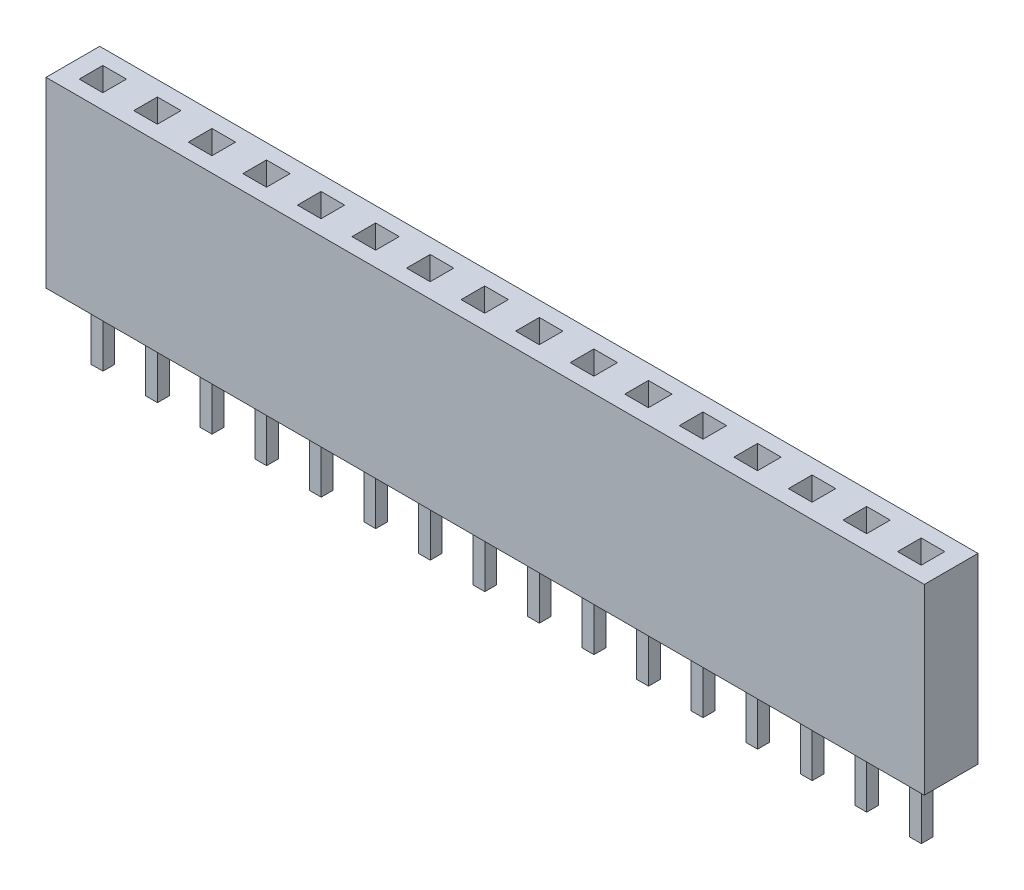
SolidWorks part; units mm, degrees
ref_plane "Front Plane" through (0, 0, 0) normal (0, 0, 1) x (1, 0, 0)
ref_plane "Top Plane" through (0, 0, 0) normal (0, 1, 0) x (1, 0, 0)
ref_plane "Right Plane" through (0, 0, 0) normal (1, 0, 0) x (0, 0, -1)
sketch "Sketch1" plane through (0, 0, 0) normal (0, 0, 1) x (1, 0, 0)
  line L1 (0, 0) -> (40.89, 0)
  line L2 (0, 0) -> (0, 8.5)
  line L3 (0, 8.5) -> (40.89, 8.5)
  line L4 (40.89, 0) -> (40.89, 8.5)
  dimension "D1" = 8.5
  dimension "D2" = 40.89
extrude "Boss-Extrude1" add sketch "Sketch1" along normal mid plane 2.5
sketch "Sketch2" plane through (0, 0, 0) normal (0, -1, 0) x (1, 0, 0)
  line L0 (0, 0) -> (40.89, 0) construction
  line L1 (40.89, 1.25) -> (40.89, -1.25) construction
  line L2 (3.385, -0.55) -> (4.485, -0.55)
  line L3 (0.845, -0.55) -> (1.945, -0.55)
  line L4 (0.845, -0.55) -> (0.845, 0.55)
  line L5 (0.845, 0.55) -> (1.945, 0.55)
  line L6 (1.945, -0.55) -> (1.945, 0.55)
  line L7 (0.845, -0.55) -> (1.945, 0.55) construction
  line L8 (0.845, 0.55) -> (1.945, -0.55) construction
  line L9 (3.385, -0.55) -> (3.385, 0.55)
  line L10 (3.385, 0.55) -> (4.485, 0.55)
  line L11 (4.485, -0.55) -> (4.485, 0.55)
  line L12 (3.385, -0.55) -> (4.485, 0.55) construction
  line L13 (3.385, 0.55) -> (4.485, -0.55) construction
  line L14 (5.925, -0.55) -> (7.025, -0.55)
  line L15 (5.925, -0.55) -> (5.925, 0.55)
  line L16 (5.925, 0.55) -> (7.025, 0.55)
  line L17 (7.025, -0.55) -> (7.025, 0.55)
  line L18 (5.925, -0.55) -> (7.025, 0.55) construction
  line L19 (5.925, 0.55) -> (7.025, -0.55) construction
  line L20 (8.465, -0.55) -> (9.565, -0.55)
  line L21 (8.465, -0.55) -> (8.465, 0.55)
  line L22 (8.465, 0.55) -> (9.565, 0.55)
  line L23 (9.565, -0.55) -> (9.565, 0.55)
  line L24 (8.465, -0.55) -> (9.565, 0.55) construction
  line L25 (8.465, 0.55) -> (9.565, -0.55) construction
  line L26 (11.005, -0.55) -> (12.105, -0.55)
  line L27 (11.005, -0.55) -> (11.005, 0.55)
  line L28 (11.005, 0.55) -> (12.105, 0.55)
  line L29 (12.105, -0.55) -> (12.105, 0.55)
  line L30 (11.005, -0.55) -> (12.105, 0.55) construction
  line L31 (11.005, 0.55) -> (12.105, -0.55) construction
  line L32 (13.545, -0.55) -> (14.645, -0.55)
  line L33 (13.545, -0.55) -> (13.545, 0.55)
  line L34 (13.545, 0.55) -> (14.645, 0.55)
  line L35 (14.645, -0.55) -> (14.645, 0.55)
  line L36 (13.545, -0.55) -> (14.645, 0.55) construction
  line L37 (13.545, 0.55) -> (14.645, -0.55) construction
  line L38 (16.085, -0.55) -> (17.185, -0.55)
  line L39 (16.085, -0.55) -> (16.085, 0.55)
  line L40 (16.085, 0.55) -> (17.185, 0.55)
  line L41 (17.185, -0.55) -> (17.185, 0.55)
  line L42 (16.085, -0.55) -> (17.185, 0.55) construction
  line L43 (16.085, 0.55) -> (17.185, -0.55) construction
  line L44 (18.625, -0.55) -> (19.725, -0.55)
  line L45 (18.625, -0.55) -> (18.625, 0.55)
  line L46 (18.625, 0.55) -> (19.725, 0.55)
  line L47 (19.725, -0.55) -> (19.725, 0.55)
  line L48 (18.625, -0.55) -> (19.725, 0.55) construction
  line L49 (18.625, 0.55) -> (19.725, -0.55) construction
  line L54 (21.165, -0.55) -> (22.265, -0.55)
  line L55 (21.165, -0.55) -> (21.165, 0.55)
  line L60 (21.165, 0.55) -> (22.265, 0.55)
  line L61 (22.265, -0.55) -> (22.265, 0.55)
  line L66 (21.165, -0.55) -> (22.265, 0.55) construction
  line L67 (21.165, 0.55) -> (22.265, -0.55) construction
  line L72 (23.705, -0.55) -> (24.805, -0.55)
  line L73 (23.705, -0.55) -> (23.705, 0.55)
  line L78 (1.395, 0) -> (3.935, 0) construction
  line L79 (23.705, 0.55) -> (24.805, 0.55)
  line L80 (24.805, -0.55) -> (24.805, 0.55)
  line L81 (23.705, -0.55) -> (24.805, 0.55) construction
  line L82 (23.705, 0.55) -> (24.805, -0.55) construction
  line L83 (26.245, -0.55) -> (27.345, -0.55)
  line L84 (26.245, -0.55) -> (26.245, 0.55)
  line L85 (26.245, 0.55) -> (27.345, 0.55)
  line L86 (27.345, -0.55) -> (27.345, 0.55)
  line L87 (26.245, -0.55) -> (27.345, 0.55) construction
  line L88 (26.245, 0.55) -> (27.345, -0.55) construction
  line L89 (28.785, -0.55) -> (29.885, -0.55)
  line L90 (28.785, -0.55) -> (28.785, 0.55)
  line L91 (28.785, 0.55) -> (29.885, 0.55)
  line L92 (29.885, -0.55) -> (29.885, 0.55)
  line L93 (28.785, -0.55) -> (29.885, 0.55) construction
  line L94 (28.785, 0.55) -> (29.885, -0.55) construction
  line L95 (31.325, -0.55) -> (32.425, -0.55)
  line L96 (31.325, -0.55) -> (31.325, 0.55)
  line L97 (31.325, 0.55) -> (32.425, 0.55)
  line L98 (32.425, -0.55) -> (32.425, 0.55)
  line L99 (31.325, -0.55) -> (32.425, 0.55) construction
  line L100 (31.325, 0.55) -> (32.425, -0.55) construction
  line L101 (33.865, -0.55) -> (34.965, -0.55)
  line L102 (33.865, -0.55) -> (33.865, 0.55)
  line L103 (33.865, 0.55) -> (34.965, 0.55)
  line L104 (34.965, -0.55) -> (34.965, 0.55)
  line L105 (33.865, -0.55) -> (34.965, 0.55) construction
  line L106 (33.865, 0.55) -> (34.965, -0.55) construction
  line L107 (36.405, -0.55) -> (37.505, -0.55)
  line L108 (36.405, -0.55) -> (36.405, 0.55)
  line L109 (36.405, 0.55) -> (37.505, 0.55)
  line L110 (37.505, -0.55) -> (37.505, 0.55)
  line L111 (36.405, -0.55) -> (37.505, 0.55) construction
  line L112 (36.405, 0.55) -> (37.505, -0.55) construction
  line L113 (38.945, -0.55) -> (40.045, -0.55)
  line L114 (38.945, -0.55) -> (38.945, 0.55)
  line L115 (38.945, 0.55) -> (40.045, 0.55)
  line L116 (40.045, -0.55) -> (40.045, 0.55)
  line L117 (38.945, -0.55) -> (40.045, 0.55) construction
  line L118 (38.945, 0.55) -> (40.045, -0.55) construction
  point P5 (1.395, 0)
  point P11 (21.715, 0)
  point P12 (3.935, 0)
  point P17 (6.475, 0)
  point P22 (9.015, 0)
  point P27 (11.555, 0)
  point P32 (14.095, 0)
  point P37 (16.635, 0)
  point P42 (19.175, 0)
  point P51 (24.255, 0)
  point P56 (26.795, 0)
  point P61 (29.335, 0)
  point P66 (31.875, 0)
  point P73 (34.415, 0)
  point P78 (36.955, 0)
  point P84 (39.495, 0)
  dimension "D1" = 1.1
  dimension "D3" = 1.395
  dimension "D4" = 2.54
  dimension "D2" = 16
extrude "Cut-Extrude1" cut sketch "Sketch2" against normal through all contours L3 L6 L5 L4 | L2 L11 L10 L9 | L14 L17 L16 L15 | L20 L23 L22 L21 | L26 L29 L28 L27 | L32 L35 L34 L33 | L38 L41 L40 L39 | L44 L47 L46 L45 | L60 L61 L54 L55 | L79 L80 L72 L73 | L85 L86 L83 L84 | L91 L92 L89 L90 | L97 L98 L95 L96 | L103 L104 L101 L102 | L109 L110 L107 L108 | L115 L116 L113 L114 region at (3.935, 0, 0) region at (1.395, 0, 0) region at (6.475, 0, 0) region at (9.015, 0, 0) region at (11.555, 0, 0) region at (14.095, 0, 0) region at (16.635, 0, 0) region at (19.175, 0, 0)
sketch "Sketch3" plane through (0, 0, 0) normal (0, -1, 0) x (1, 0, 0)
  line L1 (0, 1.25) -> (40.89, 1.25)
  line L2 (0, 1.25) -> (0, -1.25)
  line L3 (0, -1.25) -> (40.89, -1.25)
  line L4 (40.89, 1.25) -> (40.89, -1.25)
extrude "Boss-Extrude2" add sketch "Sketch3" against normal blind 1
sketch "Sketch4" plane through (0, 0, 0) normal (0, -1, 0) x (1, 0, 0)
  line L0 (1.125, 0) -> (1.675, 0) construction
  line L1 (1.125, 0.275) -> (1.675, 0.275)
  line L2 (1.125, 0.275) -> (1.125, -0.275)
  line L3 (1.125, -0.275) -> (1.675, -0.275)
  line L4 (1.675, 0.275) -> (1.675, -0.275)
  line L5 (0, 0) -> (40.89, 0) construction
  line L6 (40.89, 1.25) -> (40.89, -1.25) construction
  line L7 (0, 1.25) -> (0, -1.25) construction
  line L8 (3.665, 0.275) -> (3.665, -0.275)
  line L9 (3.665, 0.275) -> (4.215, 0.275)
  line L10 (3.665, -0.275) -> (4.215, -0.275)
  line L11 (4.215, 0.275) -> (4.215, -0.275)
  line L12 (6.205, 0.275) -> (6.205, -0.275)
  line L13 (6.205, 0.275) -> (6.755, 0.275)
  line L14 (6.205, -0.275) -> (6.755, -0.275)
  line L15 (6.755, 0.275) -> (6.755, -0.275)
  line L16 (8.745, 0.275) -> (8.745, -0.275)
  line L17 (8.745, 0.275) -> (9.295, 0.275)
  line L18 (8.745, -0.275) -> (9.295, -0.275)
  line L19 (9.295, 0.275) -> (9.295, -0.275)
  line L20 (11.285, 0.275) -> (11.285, -0.275)
  line L21 (11.285, 0.275) -> (11.835, 0.275)
  line L22 (11.285, -0.275) -> (11.835, -0.275)
  line L23 (11.835, 0.275) -> (11.835, -0.275)
  line L24 (13.825, 0.275) -> (13.825, -0.275)
  line L25 (13.825, 0.275) -> (14.375, 0.275)
  line L26 (13.825, -0.275) -> (14.375, -0.275)
  line L27 (14.375, 0.275) -> (14.375, -0.275)
  line L28 (16.365, 0.275) -> (16.365, -0.275)
  line L29 (16.365, 0.275) -> (16.915, 0.275)
  line L30 (16.365, -0.275) -> (16.915, -0.275)
  line L31 (16.915, 0.275) -> (16.915, -0.275)
  line L32 (18.905, 0.275) -> (18.905, -0.275)
  line L33 (18.905, 0.275) -> (19.455, 0.275)
  line L34 (18.905, -0.275) -> (19.455, -0.275)
  line L35 (19.455, 0.275) -> (19.455, -0.275)
  line L52 (1.125, 0.275) -> (3.665, 0.275) construction
  line L53 (21.445, 0.275) -> (21.445, -0.275)
  line L54 (21.445, 0.275) -> (21.995, 0.275)
  line L55 (21.445, -0.275) -> (21.995, -0.275)
  line L56 (21.995, 0.275) -> (21.995, -0.275)
  line L57 (23.985, 0.275) -> (23.985, -0.275)
  line L58 (23.985, 0.275) -> (24.535, 0.275)
  line L59 (23.985, -0.275) -> (24.535, -0.275)
  line L60 (24.535, 0.275) -> (24.535, -0.275)
  line L61 (26.525, 0.275) -> (26.525, -0.275)
  line L62 (26.525, 0.275) -> (27.075, 0.275)
  line L63 (26.525, -0.275) -> (27.075, -0.275)
  line L64 (27.075, 0.275) -> (27.075, -0.275)
  line L65 (29.065, 0.275) -> (29.065, -0.275)
  line L66 (29.065, 0.275) -> (29.615, 0.275)
  line L67 (29.065, -0.275) -> (29.615, -0.275)
  line L68 (29.615, 0.275) -> (29.615, -0.275)
  line L69 (31.605, 0.275) -> (31.605, -0.275)
  line L70 (31.605, 0.275) -> (32.155, 0.275)
  line L71 (31.605, -0.275) -> (32.155, -0.275)
  line L72 (32.155, 0.275) -> (32.155, -0.275)
  line L73 (34.145, 0.275) -> (34.145, -0.275)
  line L74 (34.145, 0.275) -> (34.695, 0.275)
  line L75 (34.145, -0.275) -> (34.695, -0.275)
  line L76 (34.695, 0.275) -> (34.695, -0.275)
  line L77 (36.685, 0.275) -> (36.685, -0.275)
  line L78 (36.685, 0.275) -> (37.235, 0.275)
  line L79 (36.685, -0.275) -> (37.235, -0.275)
  line L80 (37.235, 0.275) -> (37.235, -0.275)
  line L81 (39.225, 0.275) -> (39.225, -0.275)
  line L82 (39.225, 0.275) -> (39.775, 0.275)
  line L83 (39.225, -0.275) -> (39.775, -0.275)
  line L84 (39.775, 0.275) -> (39.775, -0.275)
  point P6 (1.4, 0)
  dimension "D1" = 0.55
  dimension "D2" = 1.4
  dimension "D4" = 2.54
  dimension "D3" = 16
extrude "Boss-Extrude3" add sketch "Sketch4" along normal blind 3 separate body
ref_axis "Axis1" through (1.395, 0, 0) along (0, -1, 0)
ref_axis "Axis2" through (39.495, 0, 0) along (0, -1, 0)
